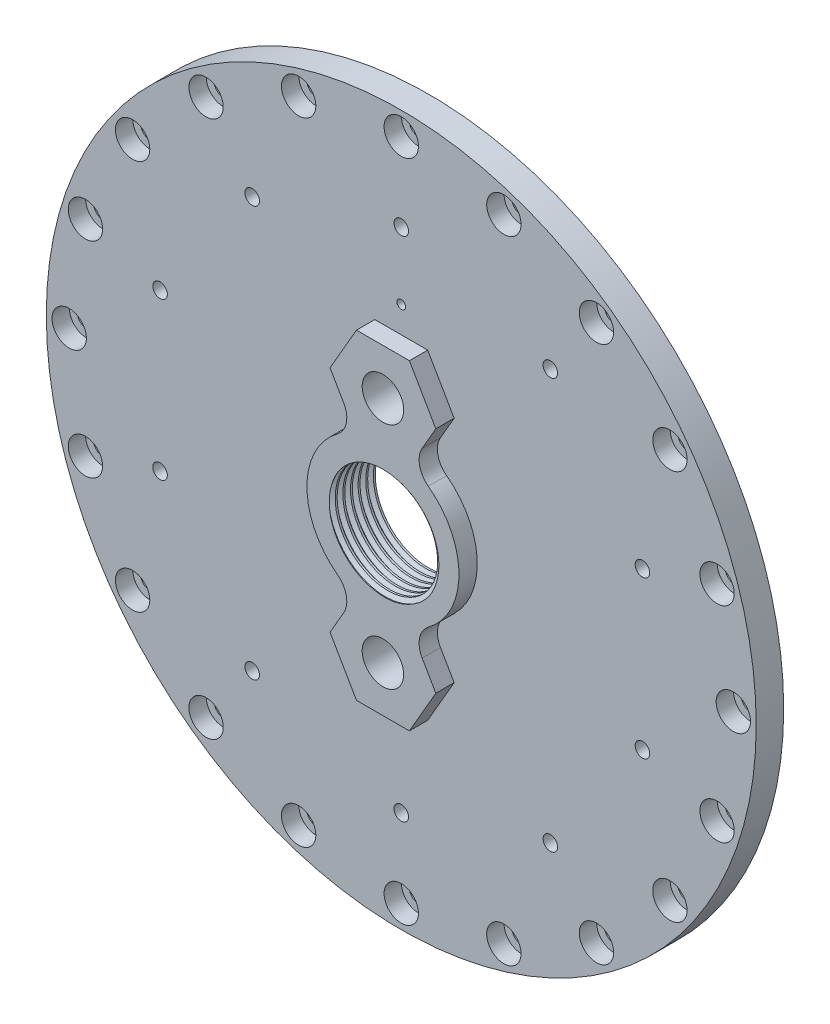
SolidWorks part; units mm, degrees
ref_plane "Front Plane" through (0, 0, 0) normal (0, 0, 1) x (1, 0, 0)
ref_plane "Top Plane" through (0, 0, 0) normal (0, 1, 0) x (1, 0, 0)
ref_plane "Right Plane" through (0, 0, 0) normal (1, 0, 0) x (0, 0, -1)
sketch "Sketch1" plane through (0, 0, 0) normal (1, 0, 0) x (0, 0, -1)
  line L0 (0, 21.082) -> (0, 98.425)
  line L1 (0, 98.425) -> (7.62, 98.425)
  line L2 (7.62, 98.425) -> (7.62, 88.6333)
  line L3 (7.62, 83.82) -> (5.08, 83.82)
  line L4 (5.08, 83.82) -> (5.08, 56.8325)
  line L5 (5.08, 56.8325) -> (7.62, 56.8325)
  line L6 (7.62, 56.8325) -> (7.62, 53.0225)
  line L7 (7.62, 14.732) -> (-5.08, 14.732)
  line L8 (-5.08, 14.732) -> (-5.08, 21.082)
  line L9 (-5.08, 21.082) -> (0, 21.082)
  line L10 (0, 0) -> (59.2702, 0) construction
  line L12 (7.62, 49.6951) -> (6.2992, 49.6951)
  line L14 (7.62, 47.0535) -> (6.2992, 47.0535)
  line L15 (6.2992, 49.6951) -> (6.2992, 47.0535)
  line L20 (7.62, 47.0535) -> (7.62, 46.0375)
  line L21 (7.62, 85.1027) -> (7.62, 83.82)
  line L22 (7.62, 50.4825) -> (7.62, 49.6951)
  line L23 (7.62, 21.59) -> (7.62, 14.732)
  line L24 (7.62, 46.0375) -> (5.08, 46.0375)
  line L26 (7.62, 21.59) -> (5.08, 21.59)
  line L27 (5.08, 46.0375) -> (5.08, 21.59)
  line L28 (7.62, 53.0225) -> (6.35, 53.0225)
  line L32 (7.62, 50.4825) -> (6.35, 50.4825)
  line L33 (6.35, 53.0225) -> (6.35, 50.4825)
  line L35 (7.62, 88.6333) -> (5.6642, 88.6333)
  line L37 (7.62, 85.1027) -> (5.6642, 85.1027)
  line L38 (5.6642, 88.6333) -> (5.6642, 85.1027)
  point P19 (6.35, 51.7525)
  point P22 (6.2992, 48.3743)
  point P31 (5.6642, 86.868)
  dimension "D1" = 196.85
  dimension "D2" = 2.54
  dimension "D3" = 7.62
  dimension "D4" = 2.54
  dimension "D5" = 113.665
  dimension "D6" = 12.7
  dimension "D7" = 29.464
  dimension "D8" = 6.35
  dimension "D9" = 2.6416
  dimension "D10" = 96.7486
  dimension "D11" = 1.3208
  dimension "D12" = 167.64
  dimension "D13" = 92.075
  dimension "D14" = 43.18
  dimension "D15" = 1.27
  dimension "D16" = 2.54
  dimension "D17" = 103.505
  dimension "D18" = 1.9558
  dimension "D19" = 3.5306
  dimension "D20" = 173.736
revolve "Revolve1" add sketch "Sketch1" angle 360 about L10 region at (0, 54.7882, -2.7116)
thread "Thread1" pitch 2.1167 method cut profile "Thread Profile1" start angle 0, offset 4.318, length 0, pitch 2.1167, diameter 29.464
ref_plane "Plane1" through (-14.732, 0, 9.398) normal (0, -1, 0) x (-1, 0, 0)
sketch "Thread Profile1" plane through (-14.732, 0, 9.398) normal (0, -1, 0) x (-1, 0, 0)
  line L0 (0, 0) -> (0, 2.1167) construction
  line L1 (0, 0) -> (1.1457, 0.6615)
  line L2 (1.1457, 0.6615) -> (1.1457, 0.926)
  line L3 (1.1457, 0.926) -> (0, 1.5875)
  line L4 (1.1457, 0.7937) -> (0, 0.7937) construction
  line L11 (0, 0) -> (0, 1.5875)
  point P2 (0, 0)
  dimension "Pitch" = 2.1167
  dimension "Profile_Angle" = 60
  dimension "Profile_Land" = 0.2646
  dimension "Profile_Height" = 1.1457
sketch "Sketch15" plane through (0, 0, 0) normal (0, 0, 1) x (1, 0, 0)
  line L10 (0, 0) -> (104.8126, 0) construction
  line L11 (7.3323, 19.05) -> (14.6647, 31.75)
  line L12 (14.6647, 31.75) -> (7.3323, 44.45)
  line L13 (7.3323, 44.45) -> (-7.3323, 44.45)
  line L14 (-7.3323, 44.45) -> (-14.6647, 31.75)
  line L15 (-14.6647, 31.75) -> (-7.3323, 19.05)
  line L16 (-7.3323, 19.05) -> (7.3323, 19.05)
  line L17 (-7.3323, -19.05) -> (7.3323, -19.05)
  line L18 (-14.6647, -31.75) -> (-7.3323, -19.05)
  line L19 (-7.3323, -44.45) -> (-14.6647, -31.75)
  line L20 (7.3323, -44.45) -> (-7.3323, -44.45)
  line L21 (14.6647, -31.75) -> (7.3323, -44.45)
  line L22 (7.3323, -19.05) -> (14.6647, -31.75)
  circle A8 centre (0, 31.75) radius 12.7 construction
  circle A9 centre (0, -31.75) radius 12.7 construction
  dimension "D2" = 63.5
  dimension "D1" = 25.4
extrude "Boss-Extrude1" add sketch "Sketch15" along normal up to surface (5.08 mm away) up to face at (21.082, 0, 5.08)
hole_wizard "1/2-20 Tapped Hole2" positions "Sketch20" profile "Sketch17" tap size "1/2-20" standard "ANSI Inch" end condition through all
sketch "Sketch20" plane through (0, 0, 5.08) normal (0, 0, 1) x (1, 0, 0)
  point P9 (0, 31.75)
  point P16 (0, -31.75)
sketch "Sketch17" plane through (0, 31.75, 5.08) normal (1, 0, 0) x (0, -1, 0)
  line L0 (0, 0) -> (0, 13.4424)
  line L1 (0, 13.4424) -> (5.7544, 13.4424)
  line L2 (5.7544, 13.4424) -> (5.7544, 0)
  line L5 (5.7544, 0) -> (0, 0)
  line L11 (0, -6.35) -> (0, 107.95) construction
  dimension "Thru Tap Drill Dia." = 11.5087
  dimension "Thru Tap Drill Depth" = 13.4424
cosmetic thread "Hole Thread3" parameters "D2"=12.7
cosmetic thread "Hole Thread4" parameters "D2"=12.7
hole_wizard "CBORE for #10 Socket Head Cap Screw1" positions "Sketch19" profile "Sketch9" counterbore size "#10" standard "ANSI Inch" end condition up to next
sketch "Sketch19" plane through (0, 0, 0) normal (0, 0, 1) x (1, 0, 0)
  circle A0 centre (0, 0) radius 92.075 construction
  point P0 (0, 92.075)
  point P16 (28.4527, 87.5685)
  point P17 (54.1203, 74.4902)
  point P18 (74.4902, 54.1203)
  point P19 (87.5685, 28.4527)
  point P20 (92.075, 0)
  point P21 (87.5685, -28.4527)
  point P22 (74.4902, -54.1203)
  point P23 (54.1203, -74.4902)
  point P24 (28.4527, -87.5685)
  point P25 (0, -92.075)
  point P26 (-28.4527, -87.5685)
  point P27 (-54.1203, -74.4902)
  point P28 (-74.4902, -54.1203)
  point P29 (-87.5685, -28.4527)
  point P30 (-92.075, 0)
  point P31 (-87.5685, 28.4527)
  point P32 (-74.4902, 54.1203)
  point P33 (-54.1203, 74.4902)
  point P34 (-28.4527, 87.5685)
  dimension "D1" = 184.15
  dimension "D2" = 20
sketch "Sketch9" plane through (0, 92.075, 0) normal (1, 0, 0) x (0, -1, 0)
  line L0 (0, 0) -> (0, 7.62)
  line L1 (0, 7.62) -> (2.5527, 7.62)
  line L3 (2.5527, 7.62) -> (2.5527, 4.826)
  line L4 (2.5527, 4.826) -> (4.7625, 4.826)
  line L5 (4.7625, 4.826) -> (4.7625, 0)
  line L7 (4.7625, 0) -> (0, 0)
  line L11 (0, -6.35) -> (0, 107.95) construction
  dimension "Thru Hole Dia." = 5.1054
  dimension "Thru Hole Depth" = 7.62
  dimension "C'Bore Dia." = 9.525
  dimension "C'Bore Depth" = 4.826
fillet "Fillet1" radius 6.35 4 edges at (-7.6711, 19.6368, 2.54) (-7.6711, -19.6368, 2.54) (7.6711, -19.6368, 2.54) (7.6711, 19.6368, 2.54)
hole_wizard "3/32 (0.09375) Dowel Hole1" positions "Sketch23" profile "Sketch22" hole size "3/32" standard "ANSI Inch" end condition up to next
sketch "Sketch23" plane through (0, 0, -6.35) normal (0, 0, -1) x (-1, 0, 0)
  line L0 (0, 50.4825) -> (0, 53.0225) construction
  circle A1 centre (0, 0) radius 50.4825 construction
  circle A2 centre (0, 0) radius 53.0225 construction
  point P0 (0, 51.7525)
  point P15 (0, 51.7525)
sketch "Sketch22" plane through (0, 51.7525, -6.35) normal (1, 0, 0) x (0, 1, 0)
  line L0 (0, 0) -> (0, 6.35)
  line L1 (0, 6.35) -> (1.1906, 6.35)
  line L2 (1.1906, 6.35) -> (1.1906, 0)
  line L5 (1.1906, 0) -> (0, 0)
  line L11 (0, -6.35) -> (0, 107.95) construction
  dimension "Thru Hole Dia." = 2.3812
  dimension "Thru Hole Depth" = 6.35
sketch "Sketch24" plane through (0, 0, 0) normal (0, 0, 1) x (1, 0, 0)
  line L0 (0, 56.8325) -> (0, 83.82) construction
  line L2 (14.4037, 90.9414) -> (0, 0) construction
  circle A0 centre (0, 0) radius 70.3263 construction
  circle A1 centre (0, 0) radius 56.8325 construction
  circle A2 centre (0, 0) radius 56.8325 construction
  circle A3 centre (0, 0) radius 83.82 construction
  arc A4 (0, 92.075) -> (28.4527, 87.5685) centre (0, 0) cw construction
  circle A5 centre (0, 0) radius 92.075 construction
  point P0 (0, 70.3263)
  point P14 (0, 70.3263)
  point P21 (0, 0)
  point P22 (0, 70.3263)
sketch "Sketch25" plane through (0, 0, 0) normal (0, 0, 1) x (1, 0, 0)
  point P0 (0, 70.3263)
hole_wizard "#10-32 Tapped Hole1" positions "Sketch25" profile "Sketch27" tap size "#10-32" standard "ANSI Inch"
sketch "Sketch27" plane through (0, 70.3263, 0) normal (1, 0, 0) x (0, -1, 0)
  line L0 (0, 0) -> (0, 4.318)
  line L1 (0, 4.318) -> (2.0193, 3.1047)
  line L2 (2.0193, 3.1047) -> (2.0193, 0)
  line L5 (2.0193, 0) -> (0, 0)
  line L10 (0, 4.318) -> (-2.0193, 3.1047) construction
  line L11 (0, -6.35) -> (0, 107.95) construction
  dimension "Tap Drill Dia." = 4.0386
  dimension "Tap Drill Depth" = 4.318
  dimension "Drill Angle" = 118
cosmetic thread "Hole Thread5" parameters "D1"=9.652, "D2"=4.826
pattern_circular "CirPattern1" count 10 over 360 about axis through (0, 0, 0) along (0, 0, 1) of "#10-32 Tapped Hole1" reverse direction yes
cosmetic thread "Hole Thread6" parameters "D1"=9.652, "D2"=4.826
cosmetic thread "Hole Thread7" parameters "D1"=9.652, "D2"=4.826
cosmetic thread "Hole Thread8" parameters "D1"=9.652, "D2"=4.826
cosmetic thread "Hole Thread9" parameters "D1"=9.652, "D2"=4.826
cosmetic thread "Hole Thread10" parameters "D1"=9.652, "D2"=4.826
cosmetic thread "Hole Thread11" parameters "D1"=9.652, "D2"=4.826
cosmetic thread "Hole Thread12" parameters "D1"=9.652, "D2"=4.826
cosmetic thread "Hole Thread13" parameters "D1"=9.652, "D2"=4.826
cosmetic thread "Hole Thread14" parameters "D1"=9.652, "D2"=4.826
